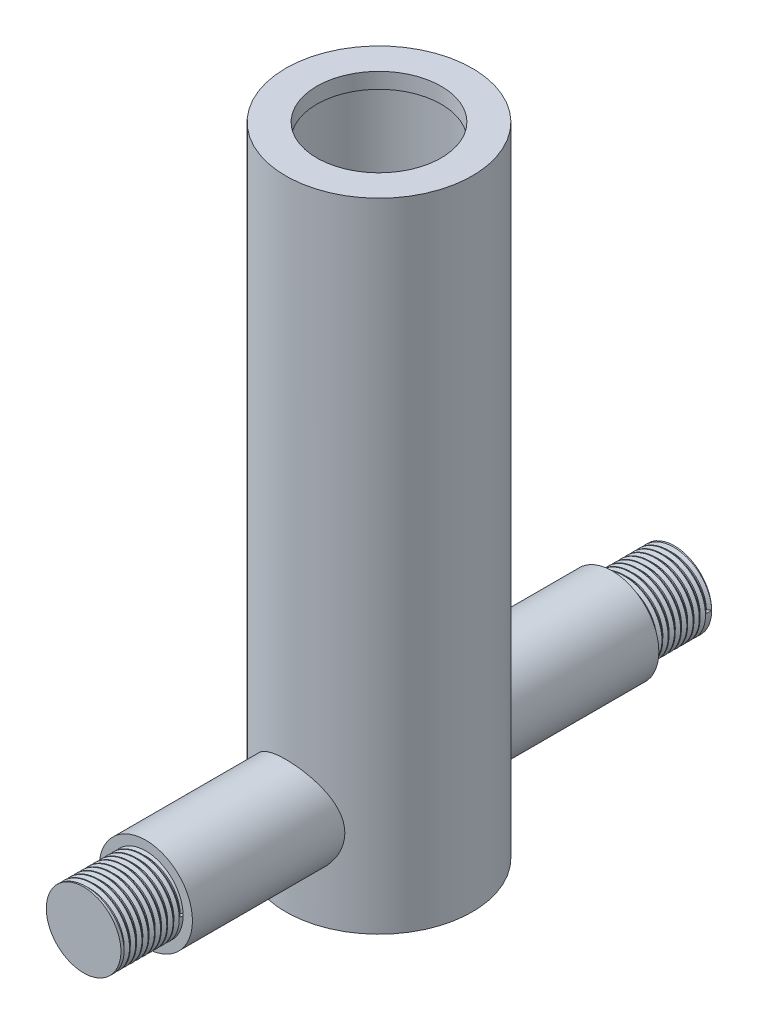
SolidWorks part; units mm, degrees
ref_plane "Front Plane" through (0, 0, 0) normal (0, 0, 1) x (1, 0, 0)
ref_plane "Top Plane" through (0, 0, 0) normal (0, 1, 0) x (1, 0, 0)
ref_plane "Right Plane" through (0, 0, 0) normal (1, 0, 0) x (0, 0, -1)
sketch "Sketch1" plane through (0, 0, 0) normal (0, 0, 1) x (1, 0, 0)
  line L0 (0, -102.5) -> (0, 102.5)
  line L1 (0, 102.5) -> (-10, 102.5)
  line L2 (-10, 102.5) -> (-10, 97.5)
  line L3 (-10, 97.5) -> (-5, 97.5)
  line L4 (-5, 97.5) -> (-5, -102.5)
  line L5 (-5, -102.5) -> (0, -102.5)
  line L6 (-30, 102.5) -> (-30, 0) construction
  point P4 (0, 0)
  point P11 (-10, 100)
  dimension "D1" = 205
  dimension "D2" = 200
  dimension "D3" = 5
  dimension "D4" = 20
  dimension "D5" = 25
revolve "Revolve1" add sketch "Sketch1" angle 360 about L6
sketch "Sketch2" plane through (0, 0, 0) normal (0, 0, 1) x (1, 0, 0)
  line L0 (-30, 102.5) -> (-30, -102.5) construction
  line L1 (0, 102.5) -> (-60, 102.5) construction
  circle A0 centre (-30, -75) radius 15
  point P6 (-30, 0)
  dimension "D1" = 30
  dimension "D2" = 75
extrude "Boss-Extrude1" add sketch "Sketch2" along normal mid plane 150
sketch "Sketch3" plane through (0, -102.5, 0) normal (0, -1, 0) x (1, 0, 0)
  circle A0 centre (-30, 0) radius 25 construction
  circle A1 centre (-30, 0) radius 25
extrude "Cut-Extrude1" cut sketch "Sketch3" against normal blind 100
sketch "Sketch4" plane through (0, 0, -75) normal (0, 0, -1) x (-1, 0, 0)
  circle A0 centre (30, -75) radius 15 construction
  circle A1 centre (30, -75) radius 15
  circle A2 centre (30, -75) radius 12
  dimension "D1" = 3
extrude "Boss-Extrude2" add sketch "Sketch4" along normal blind 20 contours A2
mirror "Mirror1" about plane through (0, 0, 0) normal (0, 0, 1) of "Boss-Extrude2"
thread "Thread1" pitch 2 method cut profile "Thread Profile1" start angle 0, offset 0, length 19, pitch 2, diameter 24
ref_plane "Plane1" through (-18, -75, -95) normal (0, -1, 0) x (1, 0, 0)
sketch "Thread Profile1" plane through (-18, -75, -95) normal (0, -1, 0) x (1, 0, 0)
  line L0 (0, 0) -> (0, 2) construction
  line L11 (0, 0) -> (0, 1.75)
  line L12 (0, 1.75) -> (-1.0825, 1.125)
  line L13 (-1.0825, 1.125) -> (-1.0825, 0.625)
  line L15 (-1.0825, 0.625) -> (0, 0)
  line L17 (-1.0825, 0.875) -> (0, 0.875) construction
  point P2 (0, 0)
  dimension "Pitch" = 2
  dimension "Profile_Angle" = 60
  dimension "Profile_Land" = 0.5
  dimension "Profile_Height" = 1.0825
thread "Thread2" pitch 2 method cut profile "Thread Profile2" start angle 0, offset 0, length 19, pitch 2, diameter 24
ref_plane "Plane2" through (-42, -75, 95) normal (0, -1, 0) x (-1, 0, 0)
sketch "Thread Profile2" plane through (-42, -75, 95) normal (0, -1, 0) x (-1, 0, 0)
  line L0 (0, 0) -> (0, 2) construction
  line L11 (0, 0) -> (0, 1.75)
  line L12 (0, 1.75) -> (-1.0825, 1.125)
  line L13 (-1.0825, 1.125) -> (-1.0825, 0.625)
  line L15 (-1.0825, 0.625) -> (0, 0)
  line L17 (-1.0825, 0.875) -> (0, 0.875) construction
  point P2 (0, 0)
  dimension "Pitch" = 2
  dimension "Profile_Angle" = 60
  dimension "Profile_Land" = 0.5
  dimension "Profile_Height" = 1.0825
